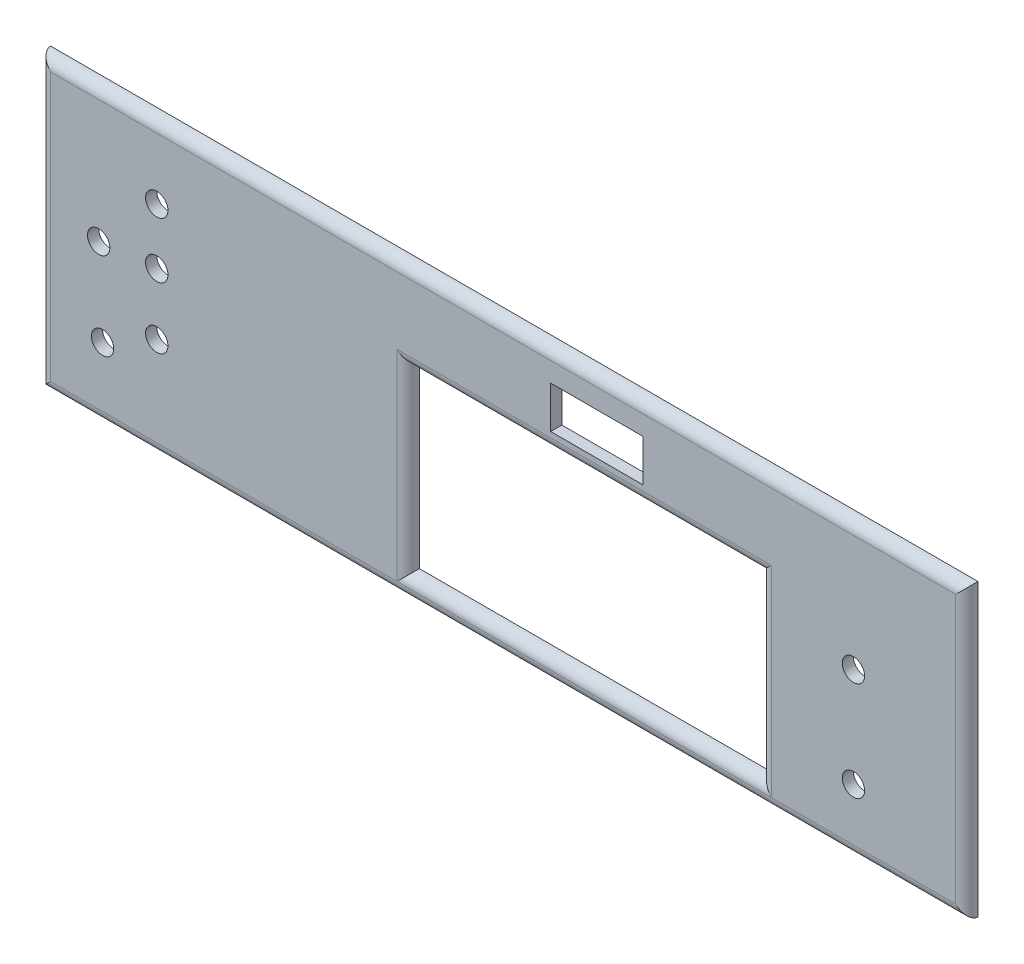
SolidWorks part; units mm, degrees
ref_plane "Přední rovina" through (0, 0, 0) normal (0, 0, 1) x (1, 0, 0)
ref_plane "Horní rovina" through (0, 0, 0) normal (0, 1, 0) x (1, 0, 0)
ref_plane "Pravá rovina" through (0, 0, 0) normal (1, 0, 0) x (0, 0, -1)
sketch "Skica1" plane through (0, 0, 0) normal (0, 0, 1) x (1, 0, 0)
  line L1 (0, 0) -> (160, 0)
  line L2 (0, 0) -> (0, 46)
  line L3 (0, 46) -> (160, 46)
  line L4 (160, 0) -> (160, 46)
  circle A0 centre (7.6, 25) radius 2
  circle A1 centre (8.3, 9.7) radius 2
  circle A2 centre (142.7, 26.2) radius 2
  circle A3 centre (142.7, 8.4) radius 2
  dimension "D3" = 4
  dimension "D4" = 8.3
  dimension "D1" = 160
  dimension "D2" = 46
  dimension "D5" = 7.6
  dimension "D6" = 9.7
  dimension "D7" = 25
  dimension "D8" = 17.3
  dimension "D9" = 8.4
  dimension "D10" = 26.2
extrude "Přidat vysunutím1" add sketch "Skica1" along normal blind 2
sketch "Skica2" plane through (0, 0, 0) normal (0, 0, -1) x (-1, 0, 0)
  line L5 (-160, 0) -> (0, 0)
  line L6 (-160, 0) -> (-160, 46)
  line L7 (-160, 46) -> (0, 46)
  line L8 (3, -3) -> (3, 49)
  line L9 (-163, -3) -> (3, -3)
  line L10 (-163, 49) -> (-163, -3)
  line L11 (3, 49) -> (-163, 49)
  line L12 (3, -3) -> (3, 49)
  line L13 (-163, -3) -> (3, -3)
  line L14 (-163, 49) -> (-163, -3)
  line L15 (3, 49) -> (-163, 49)
  line L16 (0, 0) -> (0, 46)
  dimension "D1" = 3
extrude "Přidat vysunutím4" add sketch "Skica2" against normal blind 2
sketch "Skica3" plane through (0, 0, 2) normal (0, 0, 1) x (1, 0, 0)
  line L0 (163, -3) -> (-3, -3) construction
  line L1 (63, 33) -> (126, 33)
  line L2 (63, 33) -> (63, 1)
  line L3 (63, 1) -> (126, 1)
  line L4 (126, 33) -> (126, 1)
  line L5 (163, 49) -> (163, -3) construction
  dimension "D1" = 32
  dimension "D2" = 63
  dimension "D3" = 4
  dimension "D4" = 37
extrude "Odebrat vysunutím1" cut sketch "Skica3" against normal through all
sketch "Skica4" plane through (0, 0, 2) normal (0, 0, 1) x (1, 0, 0)
  line L1 (88.5, 36) -> (105, 36)
  line L2 (88.5, 36) -> (88.5, 43.5)
  line L3 (88.5, 43.5) -> (105, 43.5)
  line L4 (105, 36) -> (105, 43.5)
  line L8 (-3, 49) -> (163, 49) construction
  line L9 (163, 49) -> (163, -3) construction
  dimension "D1" = 16.5
  dimension "D2" = 7.5
  dimension "D3" = 5.5
  dimension "D4" = 58
extrude "Odebrat vysunutím2" cut sketch "Skica4" against normal through all
fillet "Zaoblit14" radius 2 4 edges at (-3, 23, 2) (80, 49, 2) (80, -3, 2) (163, 23, 2)
sketch "Skica5" plane through (0, 0, 2) normal (0, 0, 1) x (1, 0, 0)
  circle A0 centre (18, 15) radius 2
  circle A1 centre (18, 26) radius 2
  circle A2 centre (18, 36) radius 2
  circle A3 centre (18, 15) radius 1.7657 construction
  circle A4 centre (18, 26) radius 1.79 construction
  circle A5 centre (18, 36) radius 1.6204 construction
  dimension "D1" = 4
  dimension "D2" = 4
  dimension "D3" = 4
extrude "Odebrat vysunutím3" cut sketch "Skica5" against normal through all
fillet "Zaoblit16" radius 2 4 edges at (94.5, 1, 2) (126, 17, 2) (94.5, 33, 2) (63, 17, 2)
